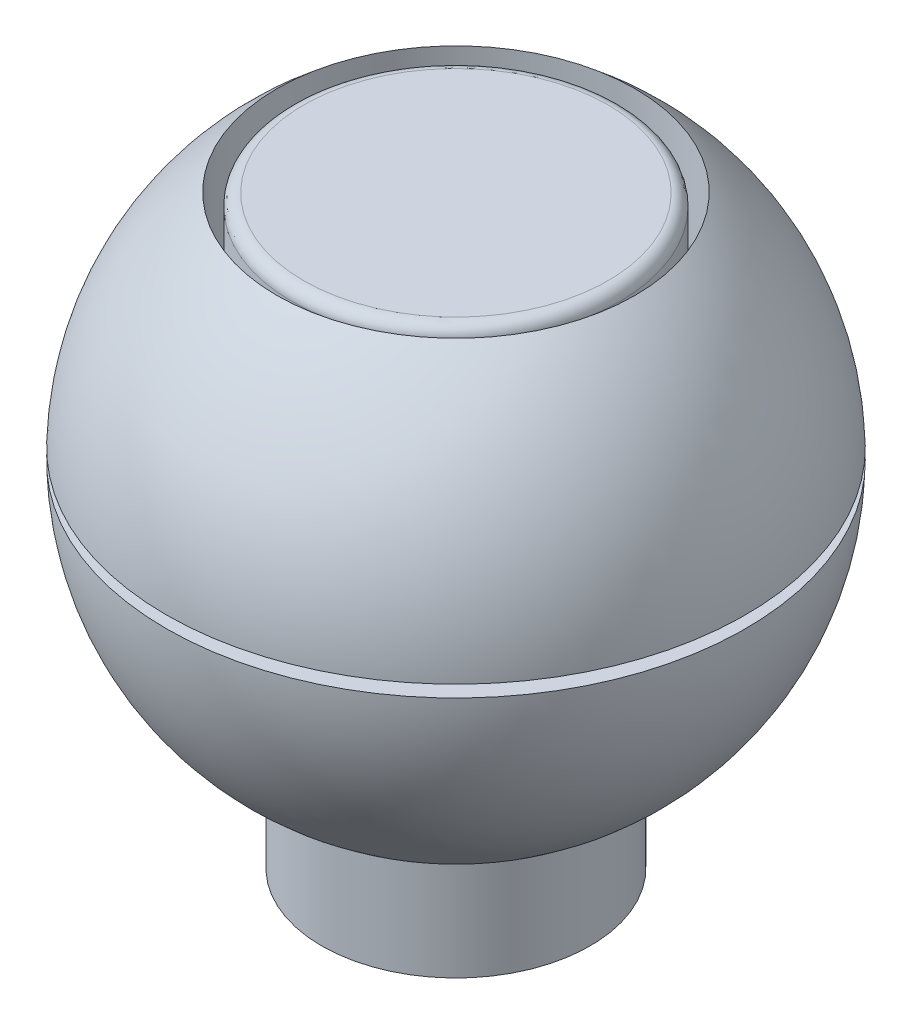
SolidWorks part; units mm, degrees
ref_plane "Front Plane" through (0, 0, 0) normal (0, 0, 1) x (1, 0, 0)
ref_plane "Top Plane" through (0, 0, 0) normal (0, 1, 0) x (1, 0, 0)
ref_plane "Right Plane" through (0, 0, 0) normal (1, 0, 0) x (0, 0, -1)
sketch "Sketch1" plane through (0, 0, 0) normal (0, 1, 0) x (1, 0, 0)
  line L0 (0, -4.85) -> (0, 4.85)
  arc A0 (0, -4.85) -> (0, 4.85) centre (0, 0) ccw
  dimension "D1" = 9.7
revolve "Revolve1" add sketch "Sketch1" angle 360 about L0
sketch "Sketch2" plane through (0, 0, 0) normal (0, 1, 0) x (1, 0, 0)
  circle A0 centre (0, 0) radius 1.6
  dimension "D1" = 3.2
extrude "Cut-Extrude1" cut sketch "Sketch2" against normal blind 10 and the other way blind 10
ref_plane "Plane1" through (0, 0.8, 0) normal (0, 1, 0) x (1, 0, 0)
sketch "Sketch3" plane through (0, 0.8, 0) normal (0, 1, 0) x (1, 0, 0)
  circle A0 centre (0, 0) radius 3
  dimension "D1" = 6
extrude "Cut-Extrude2" cut sketch "Sketch3" along normal blind 10
sketch "Sketch4" plane through (0, 0.8, 0) normal (0, 1, 0) x (1, 0, 0)
  circle A0 centre (0, 0) radius 2.75
  dimension "D1" = 5.5
extrude "Boss-Extrude1" add sketch "Sketch4" along normal blind 3 separate body
fillet "Fillet1" radius 0.2 1 edges at (0, 3.8, 2.75)
sketch "Sketch5" plane through (0, 0, 0) normal (0, 1, 0) x (1, 0, 0)
  circle A0 centre (0, 0) radius 1.6 construction
  circle A1 centre (0, 0) radius 1.6
  circle A2 centre (0, 0) radius 2.25
  dimension "D1" = 4.5
extrude "Boss-Extrude2" add sketch "Sketch5" against normal blind 6
sketch "Sketch6" plane through (0, 0, 0) normal (0, 1, 0) x (1, 0, 0)
  circle A0 centre (0, 0) radius 6.0753
extrude "Cut-Extrude3" cut sketch "Sketch6" against normal mid plane 0.2
